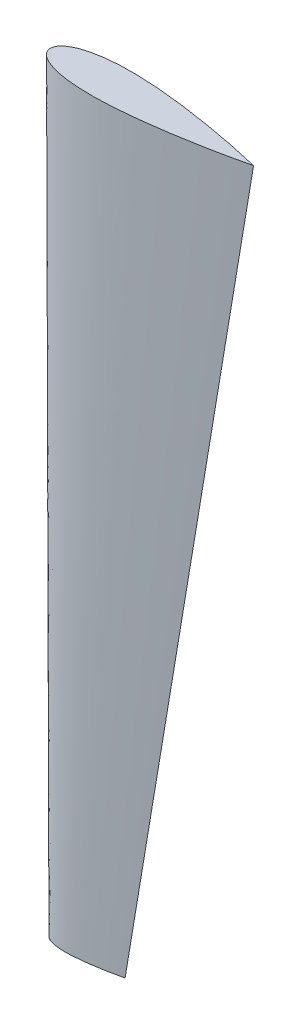
SolidWorks part; units mm, degrees
ref_plane "前视基准面" through (0, 0, 0) normal (0, 0, 1) x (1, 0, 0)
ref_plane "上视基准面" through (0, 0, 0) normal (0, 1, 0) x (1, 0, 0)
ref_plane "右视基准面" through (0, 0, 0) normal (1, 0, 0) x (0, 0, -1)
sketch "草图1" plane through (0, 0, 0) normal (0, 1, 0) x (1, 0, 0)
sketch "草图2" plane through (0, 0, 0) normal (0, 1, 0) x (1, 0, 0)
  spline S0 degree 4 poles (0, 0) (0, 0.0845) (0.0075, 0.2303) (0.0377, 0.4418) (0.1147, 0.7167) (0.2226, 0.9788) (0.3778, 1.2571) (0.5953, 1.5577) (0.8986, 1.8874) (1.3257, 2.2566) (1.9308, 2.6703) (2.7747, 3.1212) (3.9655, 3.6083) (5.5143, 4.0728) (7.7738, 4.5474) (10.6772, 4.8938) (14.0752, 5.0434) (17.9025, 4.9767) (21.7221, 4.7381) (25.531, 4.3691) (29.3286, 3.8986) (32.6413, 3.4146) (35.4744, 2.9554) (37.8297, 2.5452) (39.7126, 2.2005) (41.5893, 1.8403) (43.2341, 1.5094) (44.6327, 1.2174) (45.8112, 0.9633) (46.7266, 0.7619) (47.6959, 0.5427) (48.5599, 0.3439) (49.7194, 0.0689) (50.5622, -0.136) (51.9946, -0.4924) (53.0346, -0.7651) (54.1321, -1.0549) (54.655, -1.2016) (55.0099, -1.2985) knots 0 0 0 0 0 0.005875 0.010168 0.014828 0.019835 0.025575 0.032309 0.04061 0.050967 0.064812 0.083253 0.107121 0.14043 0.177264 0.243882 0.3105 0.377118 0.443736 0.510354 0.576972 0.64359 0.676899 0.710208 0.743517 0.776826 0.810135 0.82679 0.843444 0.860099 0.876753 0.893408 0.910062 0.932547 0.955031 0.977516 1 1 1 1 1 construction
  spline S1 degree 4 poles (0, 0) (0, 0.0845) (0.0075, 0.2303) (0.0377, 0.4418) (0.1147, 0.7167) (0.2226, 0.9788) (0.3778, 1.2571) (0.5953, 1.5577) (0.8986, 1.8874) (1.3257, 2.2566) (1.9308, 2.6703) (2.7747, 3.1212) (3.9655, 3.6083) (5.5143, 4.0728) (7.7738, 4.5474) (10.6772, 4.8938) (14.0752, 5.0434) (17.9025, 4.9767) (21.7221, 4.7381) (25.531, 4.3691) (29.3286, 3.8986) (32.6413, 3.4146) (35.4744, 2.9554) (37.8297, 2.5452) (39.7126, 2.2005) (41.5893, 1.8403) (43.2341, 1.5094) (44.6327, 1.2174) (45.8112, 0.9633) (46.7266, 0.7619) (47.6959, 0.5427) (48.5599, 0.3439) (49.3595, 0.1542) (49.7885, 0.0512) (50, 0) knots 0 0 0 0 0 0.005875 0.010168 0.014828 0.019835 0.025575 0.032309 0.04061 0.050967 0.064812 0.083253 0.107121 0.14043 0.177264 0.243882 0.3105 0.377118 0.443736 0.510354 0.576972 0.64359 0.676899 0.710208 0.743517 0.776826 0.810135 0.82679 0.843444 0.860099 0.876753 0.893408 0.910062 0.910062 0.910062 0.910062 0.910062
  spline S2 degree 4 poles (0, 0) (0, -0.0845) (0.0075, -0.2303) (0.0377, -0.4418) (0.1147, -0.7167) (0.2226, -0.9788) (0.3778, -1.2571) (0.5953, -1.5577) (0.8986, -1.8874) (1.3257, -2.2566) (1.9308, -2.6703) (2.7747, -3.1212) (3.9655, -3.6083) (5.5143, -4.0728) (7.7738, -4.5474) (10.6772, -4.8938) (14.0752, -5.0434) (17.9025, -4.9767) (21.7221, -4.7381) (25.531, -4.3691) (29.3286, -3.8986) (32.6413, -3.4146) (35.4744, -2.9554) (37.8297, -2.5452) (39.7126, -2.2005) (41.5893, -1.8403) (43.2341, -1.5094) (44.6327, -1.2174) (45.8112, -0.9633) (46.7266, -0.7619) (47.6959, -0.5427) (48.5599, -0.3439) (49.7194, -0.0689) (50.5622, 0.136) (51.9946, 0.4924) (53.0346, 0.7651) (54.1321, 1.0549) (54.655, 1.2016) (55.0099, 1.2985) knots 0 0 0 0 0 0.005875 0.010168 0.014828 0.019835 0.025575 0.032309 0.04061 0.050967 0.064812 0.083253 0.107121 0.14043 0.177264 0.243882 0.3105 0.377118 0.443736 0.510354 0.576972 0.64359 0.676899 0.710208 0.743517 0.776826 0.810135 0.82679 0.843444 0.860099 0.876753 0.893408 0.910062 0.932547 0.955031 0.977516 1 1 1 1 1 construction
  spline S3 degree 4 poles (0, 0) (0, -0.0845) (0.0075, -0.2303) (0.0377, -0.4418) (0.1147, -0.7167) (0.2226, -0.9788) (0.3778, -1.2571) (0.5953, -1.5577) (0.8986, -1.8874) (1.3257, -2.2566) (1.9308, -2.6703) (2.7747, -3.1212) (3.9655, -3.6083) (5.5143, -4.0728) (7.7738, -4.5474) (10.6772, -4.8938) (14.0752, -5.0434) (17.9025, -4.9767) (21.7221, -4.7381) (25.531, -4.3691) (29.3286, -3.8986) (32.6413, -3.4146) (35.4744, -2.9554) (37.8297, -2.5452) (39.7126, -2.2005) (41.5893, -1.8403) (43.2341, -1.5094) (44.6327, -1.2174) (45.8112, -0.9633) (46.7266, -0.7619) (47.6959, -0.5427) (48.5599, -0.3439) (49.3595, -0.1542) (49.7885, -0.0512) (50, 0) knots 0 0 0 0 0 0.005875 0.010168 0.014828 0.019835 0.025575 0.032309 0.04061 0.050967 0.064812 0.083253 0.107121 0.14043 0.177264 0.243882 0.3105 0.377118 0.443736 0.510354 0.576972 0.64359 0.676899 0.710208 0.743517 0.776826 0.810135 0.82679 0.843444 0.860099 0.876753 0.893408 0.910062 0.910062 0.910062 0.910062 0.910062
  point P0 (-134.2937, 56.1296)
ref_plane "基准面1" through (0, 514, 0) normal (0, 1, 0) x (1, 0, 0)
sketch "草图3" plane through (0, 514, 0) normal (0, 1, 0) x (1, 0, 0)
  spline S0 degree 4 poles (0, 0) (-0.0001, 0.2298) (0.0203, 0.6264) (0.1025, 1.2017) (0.3119, 1.9493) (0.6054, 2.6624) (1.0277, 3.4193) (1.6193, 4.2369) (2.4441, 5.1339) (3.606, 6.1379) (5.2519, 7.2631) (7.5472, 8.4896) (10.7862, 9.8146) (14.9989, 11.0781) (21.1449, 12.369) (29.042, 13.3111) (38.2844, 13.718) (48.6948, 13.5365) (59.0841, 12.8875) (69.4444, 11.884) (79.7734, 10.6042) (88.7848, 9.2877) (96.4895, 8.039) (102.8981, 6.9228) (108.0157, 5.9859) (112.489, 5.127) (116.3133, 4.364) (119.5039, 3.7073) (121.7216, 3.2407) (123.6472, 2.827) (125.5217, 2.4193) (127.1743, 2.0523) (128.6514, 1.7222) (130.7201, 1.2477) (132.3169, 0.8806) (134.8257, 0.2845) (136.4692, -0.1123) (139.0746, -0.7527) (141.4723, -1.3578) (144.137, -2.0456) (146.3998, -2.6501) (148.1305, -3.1196) (148.9616, -3.3487) (149.3869, -3.4663) (149.6008, -3.5256) knots 0 0 0 0 0 0.005875 0.010168 0.014828 0.019835 0.025575 0.032309 0.04061 0.050967 0.064812 0.083253 0.107121 0.14043 0.177264 0.243882 0.3105 0.377118 0.443736 0.510354 0.576972 0.64359 0.676899 0.710208 0.743517 0.776826 0.793481 0.810135 0.82679 0.835117 0.843444 0.860099 0.868426 0.876753 0.893408 0.910062 0.921305 0.932547 0.955031 0.977516 0.988758 0.994379 1 1 1 1 1 construction
  spline S1 degree 4 poles (0, 0) (-0.0001, 0.2298) (0.0203, 0.6264) (0.1025, 1.2017) (0.3119, 1.9493) (0.6054, 2.6624) (1.0277, 3.4193) (1.6193, 4.2369) (2.4441, 5.1339) (3.606, 6.1379) (5.2519, 7.2631) (7.5472, 8.4896) (10.7862, 9.8146) (14.9989, 11.0781) (21.1449, 12.369) (29.042, 13.3111) (38.2844, 13.718) (48.6948, 13.5365) (59.0841, 12.8875) (69.4444, 11.884) (79.7734, 10.6042) (88.7848, 9.2877) (96.4895, 8.039) (102.8981, 6.9228) (108.0157, 5.9859) (112.489, 5.127) (116.3133, 4.364) (119.5039, 3.7073) (121.7216, 3.2407) (123.6472, 2.827) (125.5217, 2.4193) (127.1743, 2.0523) (128.6514, 1.7222) (130.7201, 1.2477) (132.3169, 0.8806) (134.2923, 0.4112) (135.4247, 0.1394) (136, 0) knots 0 0 0 0 0 0.005875 0.010168 0.014828 0.019835 0.025575 0.032309 0.04061 0.050967 0.064812 0.083253 0.107121 0.14043 0.177264 0.243882 0.3105 0.377118 0.443736 0.510354 0.576972 0.64359 0.676899 0.710208 0.743517 0.776826 0.793481 0.810135 0.82679 0.835117 0.843444 0.860099 0.868426 0.876753 0.893408 0.910062 0.910062 0.910062 0.910062 0.910062
  spline S2 degree 4 poles (0, 0) (-0.0001, -0.2298) (0.0203, -0.6264) (0.1025, -1.2017) (0.3119, -1.9493) (0.6054, -2.6624) (1.0277, -3.4193) (1.6193, -4.2369) (2.4441, -5.1339) (3.606, -6.1379) (5.2519, -7.2631) (7.5472, -8.4896) (10.7862, -9.8146) (14.9989, -11.0781) (21.1449, -12.369) (29.042, -13.3111) (38.2844, -13.718) (48.6948, -13.5365) (59.0841, -12.8875) (69.4444, -11.884) (79.7734, -10.6042) (88.7848, -9.2877) (96.4895, -8.039) (102.8981, -6.9228) (108.0157, -5.9859) (112.489, -5.127) (116.3133, -4.364) (119.5039, -3.7073) (121.7216, -3.2407) (123.6472, -2.827) (125.5217, -2.4193) (127.1743, -2.0523) (128.6514, -1.7222) (130.7201, -1.2477) (132.3169, -0.8806) (134.8257, -0.2845) (136.4692, 0.1123) (139.0746, 0.7527) (141.4723, 1.3578) (144.137, 2.0456) (146.3998, 2.6501) (148.1305, 3.1196) (148.9616, 3.3487) (149.3869, 3.4663) (149.6008, 3.5256) knots 0 0 0 0 0 0.005875 0.010168 0.014828 0.019835 0.025575 0.032309 0.04061 0.050967 0.064812 0.083253 0.107121 0.14043 0.177264 0.243882 0.3105 0.377118 0.443736 0.510354 0.576972 0.64359 0.676899 0.710208 0.743517 0.776826 0.793481 0.810135 0.82679 0.835117 0.843444 0.860099 0.868426 0.876753 0.893408 0.910062 0.921305 0.932547 0.955031 0.977516 0.988758 0.994379 1 1 1 1 1 construction
  spline S3 degree 4 poles (0, 0) (-0.0001, -0.2298) (0.0203, -0.6264) (0.1025, -1.2017) (0.3119, -1.9493) (0.6054, -2.6624) (1.0277, -3.4193) (1.6193, -4.2369) (2.4441, -5.1339) (3.606, -6.1379) (5.2519, -7.2631) (7.5472, -8.4896) (10.7862, -9.8146) (14.9989, -11.0781) (21.1449, -12.369) (29.042, -13.3111) (38.2844, -13.718) (48.6948, -13.5365) (59.0841, -12.8875) (69.4444, -11.884) (79.7734, -10.6042) (88.7848, -9.2877) (96.4895, -8.039) (102.8981, -6.9228) (108.0157, -5.9859) (112.489, -5.127) (116.3133, -4.364) (119.5039, -3.7073) (121.7216, -3.2407) (123.6472, -2.827) (125.5217, -2.4193) (127.1743, -2.0523) (128.6514, -1.7222) (130.7201, -1.2477) (132.3169, -0.8806) (134.2923, -0.4112) (135.4247, -0.1394) (136, 0) knots 0 0 0 0 0 0.005875 0.010168 0.014828 0.019835 0.025575 0.032309 0.04061 0.050967 0.064812 0.083253 0.107121 0.14043 0.177264 0.243882 0.3105 0.377118 0.443736 0.510354 0.576972 0.64359 0.676899 0.710208 0.743517 0.776826 0.793481 0.810135 0.82679 0.835117 0.843444 0.860099 0.868426 0.876753 0.893408 0.910062 0.910062 0.910062 0.910062 0.910062
  point P0 (-177.183, 7.2502)
loft "放样1" add profiles "草图2", "草图3" connector at (0, 0, 0) connector at (0, 514, 0)
